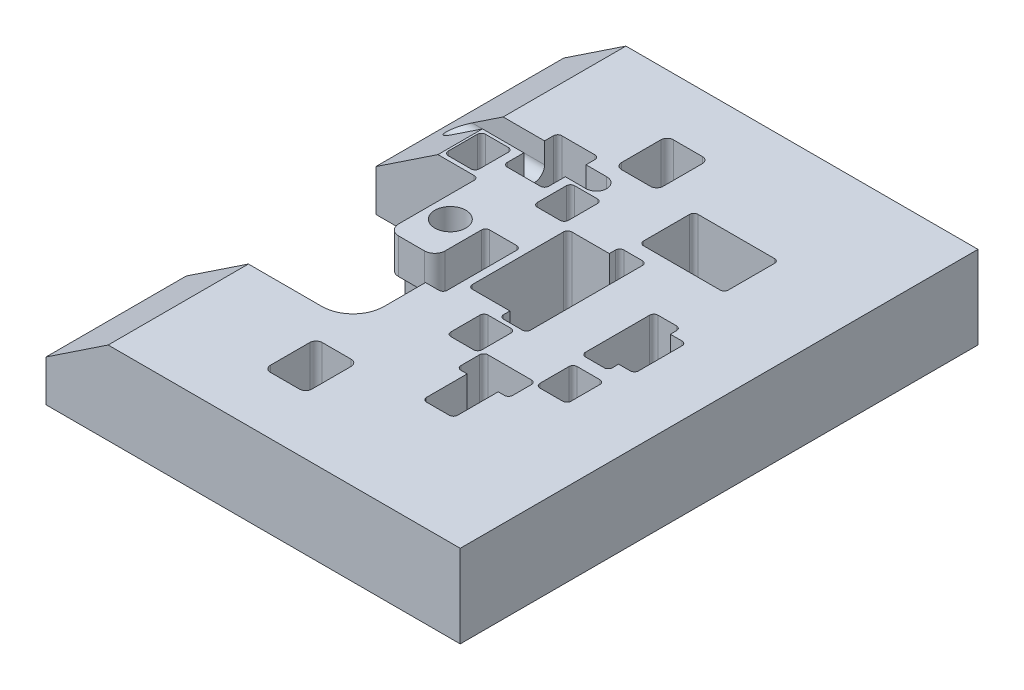
SolidWorks part; units mm, degrees
material "K110"
ref_plane "Front Plane" through (0, 0, 0) normal (0, 0, 1) x (1, 0, 0)
ref_plane "Top Plane" through (0, 0, 0) normal (0, 1, 0) x (1, 0, 0)
ref_plane "Right Plane" through (0, 0, 0) normal (1, 0, 0) x (0, 0, -1)
sketch "Sketch1" plane through (0, 0, 0) normal (0, 1, 0) x (1, 0, 0)
  line L1 (-100, -125) -> (100, -125)
  line L2 (-100, -125) -> (-100, 125)
  line L3 (-100, 125) -> (100, 125)
  line L4 (100, -125) -> (100, 125)
  line L5 (-100, -125) -> (100, 125) construction
  line L6 (-100, 125) -> (100, -125) construction
  point P0 (0, 0)
  dimension "D1" = 250
  dimension "D2" = 200
extrude "Boss-Extrude1" add sketch "Sketch1" along normal blind 40
sketch "Sketch2" plane through (0, 40, 0) normal (0, 1, 0) x (1, 0, 0)
  line L0 (17.25, 55.73) -> (55.25, 55.73) construction
  line L1 (15.75, 32.73) -> (15.75, -12.27) construction
  line L2 (58.25, 13.73) -> (58.25, -8.27) construction
  line L3 (30.25, -47.4) -> (42.25, -47.4) construction
  line L4 (17.25, 55.73) -> (55.25, 55.73)
  line L5 (15.75, 32.73) -> (15.75, -12.27)
  line L6 (58.25, 13.73) -> (58.25, -8.27)
  line L7 (30.25, -47.4) -> (42.25, -47.4)
sketch "Sketch3" plane through (0, 40, 0) normal (0, 1, 0) x (1, 0, 0)
  line L0 (30.25, -47.4) -> (42.25, -47.4) construction
  line L1 (28.75, -72.03) -> (43.75, -72.03)
  line L2 (28.75, -72.03) -> (28.75, -50.4)
  line L3 (23.75, -37.4) -> (48.75, -37.4)
  line L4 (43.75, -72.03) -> (43.75, -50.4)
  line L8 (36.25, -37.4) -> (36.25, -72.03) construction
  line L9 (36.25, 69.53) -> (36.25, -69.53) construction
  line L11 (43.75, -50.4) -> (48.75, -50.4)
  line L12 (48.75, -50.4) -> (48.75, -37.4)
  line L13 (28.75, -50.4) -> (23.75, -50.4)
  line L14 (23.75, -50.4) -> (23.75, -37.4)
  line L15 (66.38, -69.53) -> (-4.87, -69.53) construction
  dimension "D1" = 10
  dimension "D2" = 15
  dimension "D3" = 3
  dimension "D4" = 25
  dimension "D5" = 2.5
extrude "Cut-Extrude2" cut sketch "Sketch3" against normal up to next contours L3 L12 L11 L4 L1 L2 L13 L14
fillet "Fillet3" radius 2 6 edges at (43.75, 20, 72.03) (28.75, 20, 72.03) (48.75, 20, 50.4) (23.75, 20, 50.4) (48.75, 20, 37.4) (23.75, 20, 37.4)
sketch "Sketch4" plane through (0, 40, 0) normal (0, 1, 0) x (1, 0, 0)
  line L0 (48.25, -14.77) -> (61.25, -14.77)
  line L5 (61.25, -14.77) -> (61.25, -9.77)
  line L6 (64.38, 13.73) -> (58.25, 13.73) construction
  line L7 (66.38, 69.53) -> (66.38, -69.53) construction
  line L8 (66.38, 2.73) -> (51.7072, 2.73) construction
  line L9 (66.38, -6.27) -> (66.38, 11.73) construction
  line L10 (61.25, -9.77) -> (68.88, -9.77)
  line L11 (68.88, -9.77) -> (68.88, 15.23)
  line L13 (68.88, 15.23) -> (61.25, 15.23)
  line L14 (61.25, 15.23) -> (61.25, 20.23)
  line L15 (61.25, 20.23) -> (48.25, 20.23)
  line L16 (48.25, 20.23) -> (48.25, -14.77)
  line L17 (58.25, 13.73) -> (58.25, -8.27) construction
  dimension "D1" = 1.5
  dimension "D2" = 5
  dimension "D3" = 2.5
  dimension "D4" = 10
  dimension "D5" = 3
extrude "Cut-Extrude3" cut sketch "Sketch4" against normal up to next
fillet "Fillet4" radius 2 6 edges at (68.88, 20, 9.77) (68.88, 20, -15.23) (61.25, 20, -20.23) (48.25, 20, -20.23) (48.25, 20, 14.77) (61.25, 20, 14.77)
sketch "Sketch5" plane through (0, 40, 0) normal (0, 1, 0) x (1, 0, 0)
  line L0 (-7.37, -13.77) -> (12.75, -13.77)
  line L2 (12.75, -18.77) -> (25.75, -18.77)
  line L3 (25.75, -18.77) -> (25.75, 39.23)
  line L4 (25.75, 39.23) -> (12.75, 39.23)
  line L5 (12.75, 39.23) -> (12.75, 34.23)
  line L6 (12.75, 34.23) -> (-7.37, 34.23)
  line L7 (-7.37, 34.23) -> (-7.37, -13.77)
  line L8 (15.75, 32.73) -> (15.75, -12.27) construction
  line L9 (-4.87, 69.53) -> (-4.87, -69.53) construction
  line L10 (-4.87, 10.23) -> (25.75, 10.23) construction
  line L11 (-4.87, 26.73) -> (-4.87, -6.27) construction
  line L12 (12.75, -18.77) -> (12.75, -13.77)
  line L13 (1.13, -12.27) -> (15.75, -12.27) construction
  line L17 (-18, -8.27) -> (-18, 13.73) construction
  line L18 (-18, 2.73) -> (-15, 2.73) construction
  dimension "D1" = 3
  dimension "D2" = 10
  dimension "D3" = 2.5
  dimension "D4" = 1.5
  dimension "D5" = 5
extrude "Cut-Extrude4" cut sketch "Sketch5" against normal up to next
fillet "Fillet5" radius 2 6 edges at (25.75, 20, -39.23) (12.75, 20, 18.77) (25.75, 20, 18.77) (-7.37, 20, 13.77) (12.75, 20, -39.23) (-7.37, 20, -34.23)
sketch "Sketch6" plane through (0, 40, 0) normal (0, 1, 0) x (1, 0, 0)
  line L0 (15.75, 72.03) -> (15.75, 45.73)
  line L3 (15.75, 45.73) -> (56.75, 45.73)
  line L6 (56.75, 45.73) -> (56.75, 72.03)
  line L7 (56.75, 72.03) -> (15.75, 72.03)
  line L8 (36.25, 69.53) -> (36.25, 45.73) construction
  line L9 (36.25, 69.53) -> (36.25, -69.53) construction
  line L10 (66.38, 69.53) -> (-4.87, 69.53) construction
  line L12 (17.25, 55.73) -> (55.25, 55.73) construction
  dimension "D1" = 2.5
  dimension "D2" = 41
  dimension "D5" = 10
extrude "Cut-Extrude5" cut sketch "Sketch6" against normal up to next
fillet "Fillet6" radius 2 4 edges at (15.75, 20, -72.03) (56.75, 20, -72.03) (15.75, 20, -45.73) (56.75, 20, -45.73)
sketch "Sketch7" plane through (0, 40, 0) normal (0, 1, 0) x (1, 0, 0)
  line L0 (57.75, -29.77) -> (57.75, -32.27) construction
  line L3 (60.25, -29.77) -> (55.25, -29.77) construction
  line L4 (60.25, -27.27) -> (60.25, -32.27) construction
  line L5 (55.25, -11.27) -> (55.25, -38.4) construction
  line L7 (63.25, -20.77) -> (52.25, -20.77)
  line L8 (65.25, -22.77) -> (65.25, -36.77)
  line L9 (63.25, -38.77) -> (52.25, -38.77)
  line L10 (50.25, -22.77) -> (50.25, -36.77)
  arc A2 (52.25, -38.77) -> (50.25, -36.77) centre (52.25, -36.77) cw
  arc A3 (65.25, -36.77) -> (63.25, -38.77) centre (63.25, -36.77) cw
  arc A4 (63.25, -20.77) -> (65.25, -22.77) centre (63.25, -22.77) cw
  arc A5 (52.25, -20.77) -> (50.25, -22.77) centre (52.25, -22.77) ccw
  point P14 (50.25, -38.77)
  point P17 (65.25, -38.77)
  point P20 (65.25, -20.77)
  dimension "D4" = 2
  dimension "D1" = 2.5
  dimension "D2" = 18
  dimension "D3" = 15
  dimension "D5" = 9
extrude "Cut-Extrude6" cut sketch "Sketch7" against normal up to next
sketch "Sketch8" plane through (0, 40, 0) normal (0, 1, 0) x (1, 0, 0)
  line L0 (12.25, -29.77) -> (17.25, -29.77) construction
  line L3 (12.25, -32.27) -> (12.25, -27.27) construction
  line L4 (63.25, -20.77) -> (52.25, -20.77) construction
  line L7 (17.25, -38.4) -> (17.25, -13.77) construction
  line L8 (14.75, -29.77) -> (14.75, -32.27) construction
  line L9 (52.25, -38.77) -> (63.25, -38.77) construction
  line L10 (9.25, -20.77) -> (20.25, -20.77)
  line L11 (7.25, -22.77) -> (7.25, -36.77)
  line L12 (9.25, -38.77) -> (20.25, -38.77)
  line L13 (22.25, -22.77) -> (22.25, -36.77)
  arc A2 (7.25, -36.77) -> (9.25, -38.77) centre (9.25, -36.77) ccw
  arc A3 (20.25, -38.77) -> (22.25, -36.77) centre (20.25, -36.77) ccw
  arc A4 (20.25, -20.77) -> (22.25, -22.77) centre (20.25, -22.77) cw
  arc A5 (9.25, -20.77) -> (7.25, -22.77) centre (9.25, -22.77) ccw
  dimension "D1" = 2.5
  dimension "D2" = 2
extrude "Cut-Extrude7" cut sketch "Sketch8" against normal up to next
sketch "Sketch21" plane through (0, 40, 0) normal (0, 1, 0) x (1, 0, 0)
  line L0 (-21, 55.73) -> (-21, 16.73) construction
  line L3 (-24, 54.23) -> (-13, 54.23)
  line L4 (-26, 52.23) -> (-26, 38.23)
  line L5 (-24, 36.23) -> (-13, 36.23)
  line L6 (-11, 52.23) -> (-11, 38.23)
  line L7 (-21, 55.73) -> (-59, 55.73) construction
  line L9 (-16, 45.23) -> (-21, 45.23) construction
  line L10 (-18.5, 45.23) -> (-18.5, 54.23) construction
  line L11 (-40, 55.73) -> (-40, 36.23) construction
  line L12 (-16, 42.73) -> (-16, 47.73) construction
  line L16 (-69, 52.23) -> (-69, 38.23)
  line L17 (-56, 36.23) -> (-67, 36.23)
  line L18 (-54, 52.23) -> (-54, 38.23)
  line L19 (-56, 54.23) -> (-67, 54.23)
  arc A2 (-26, 38.23) -> (-24, 36.23) centre (-24, 38.23) ccw
  arc A3 (-13, 36.23) -> (-11, 38.23) centre (-13, 38.23) ccw
  arc A4 (-13, 54.23) -> (-11, 52.23) centre (-13, 52.23) cw
  arc A5 (-24, 54.23) -> (-26, 52.23) centre (-24, 52.23) ccw
  arc A6 (-56, 54.23) -> (-54, 52.23) centre (-56, 52.23) cw
  arc A7 (-67, 54.23) -> (-69, 52.23) centre (-67, 52.23) ccw
  arc A8 (-67, 36.23) -> (-69, 38.23) centre (-67, 38.23) cw
  arc A9 (-54, 38.23) -> (-56, 36.23) centre (-56, 38.23) cw
  dimension "D4" = 15
  dimension "D2" = 2
  dimension "D1" = 2.5
  dimension "D3" = 18
extrude "Cut-Extrude12" cut sketch "Sketch21" against normal up to next
sketch "Sketch22" plane through (0, 40, 0) normal (0, 1, 0) x (1, 0, 0)
  line L0 (-100, 125) -> (-100, -125) construction
  line L1 (-100, 55.73) -> (-15, 55.73)
  line L2 (-100, 55.73) -> (-100, 65.726)
  line L3 (-100, 65.726) -> (-15, 65.726)
  line L4 (-15, 55.73) -> (-15, 65.726)
  line L5 (-21, 55.73) -> (-59, 55.73) construction
  line L6 (-59, 63.776) -> (-21, 63.776) construction
  line L7 (-21, 55.73) -> (-21, 61.5256) construction
  line L8 (-15, 60.728) -> (-100, 60.728) construction
  dimension "D1" = 1.95
  dimension "D2" = 6
ref_plane "Plane1" through (0, 0, -60.728) normal (0, 0, -1) x (-1, 0, 0)
sketch "Sketch24" plane through (0, 0, -60.728) normal (0, 0, -1) x (-1, 0, 0)
  line L0 (15, 40) -> (15, 35)
  line L1 (15, 40) -> (100, 40) construction
  line L2 (25, 25) -> (100, 25)
  line L3 (100, 40) -> (100, 0) construction
  line L4 (15, 40) -> (100, 40)
  line L5 (100, 40) -> (100, 25)
  arc A0 (15, 35) -> (25, 25) centre (25, 35) ccw
  dimension "D2" = 10
  dimension "D1" = 15
extrude "Cut-Extrude15" cut sketch "Sketch24" against normal mid plane 10
fillet "Fillet9" 2 edges at (-62.5, 25, -55.728) (-62.5, 25, -65.728) type full round first side face at (-50.5858, 32.5858, -55.728) second side face at (-50.5858, 32.5858, -65.728) middle face at (-62.5, 25, -60.728)
sketch "Sketch23" plane through (0, 40, 0) normal (0, 1, 0) x (1, 0, 0)
  line L0 (-40, 55.73) -> (-40, 45.73) construction
  line L1 (-48, 72.03) -> (-32, 72.03)
  line L2 (-50, 70.03) -> (-50, 47.73)
  line L3 (-48, 45.73) -> (-32, 45.73)
  line L4 (-30, 70.03) -> (-30, 47.73)
  line L5 (-21, 55.73) -> (-59, 55.73) construction
  line L6 (17.75, 45.73) -> (54.75, 45.73) construction
  line L7 (54.75, 72.03) -> (17.75, 72.03) construction
  arc A0 (-50, 47.73) -> (-48, 45.73) centre (-48, 47.73) ccw
  arc A1 (-48, 72.03) -> (-50, 70.03) centre (-48, 70.03) ccw
  arc A2 (-32, 72.03) -> (-30, 70.03) centre (-32, 70.03) cw
  arc A3 (-32, 45.73) -> (-30, 47.73) centre (-32, 47.73) ccw
  point P14 (-50, 45.73)
  point P21 (-30, 45.73)
  dimension "D2" = 2
  dimension "D1" = 20
extrude "Cut-Extrude14" cut sketch "Sketch23" against normal up to next
sketch "Sketch26" plane through (0, 40, 0) normal (0, 1, 0) x (1, 0, 0)
  line L0 (-100, 55.728) -> (-100, -125) construction
  line L1 (-100, 34.23) -> (-50.5, 34.23)
  line L2 (-100, 34.23) -> (-100, -57.27)
  line L3 (-100, -57.27) -> (-19.5, -57.27)
  line L4 (-19.5, -22.27) -> (-19.5, -57.27)
  line L5 (-60.5, 32.73) -> (-66.5, 32.73) construction
  line L6 (-50.5, 34.23) -> (-50.5, -9.27)
  line L7 (-50.5, -9.27) -> (-28, -9.27)
  line L8 (-59, -19.27) -> (-21, -19.27) construction
  line L9 (-21, -11.27) -> (-21, -19.27) construction
  line L10 (-28, -9.27) -> (-28, 15.23)
  line L11 (-60.5, -12.27) -> (-60.5, 32.73) construction
  line L12 (-19.5, -22.27) -> (-11, -22.27)
  line L13 (-11, -22.27) -> (-11, 15.23)
  line L14 (-28, 15.23) -> (-11, 15.23)
  line L15 (-18, -8.27) -> (-18, 13.73) construction
  line L16 (-12, 13.73) -> (-18, 13.73) construction
  dimension "D1" = 1.5
  dimension "D2" = 10
  dimension "D3" = 1.5
  dimension "D4" = 35
  dimension "D5" = 10
  dimension "D6" = 1.5
  dimension "D7" = 3
  dimension "D8" = 10
  dimension "D9" = 7
extrude "Cut-Extrude16" cut sketch "Sketch26" against normal up to next contours L1 L6 L7 L10 L14 L13 L12 L4 L3 L2
fillet "Fillet10" radius 2 4 edges at (-11, 20, 22.27) (-50.5, 20, -34.23) (-11, 20, -15.23) (-28, 20, -15.23)
sketch "Sketch27" plane through (-50.5, 0, 0) normal (-1, 0, 0) x (0, 0, 1)
  line L0 (-32.23, 0) -> (9.27, 0) construction
  line L1 (1.27, 0) -> (9.27, 0)
  line L2 (1.27, 0) -> (1.27, 23)
  line L3 (1.27, 23) -> (9.27, 23)
  line L4 (9.27, 0) -> (9.27, 23)
  line L5 (9.27, 23) -> (9.27, 0) construction
  dimension "D1" = 23
  dimension "D2" = 8
extrude "Cut-Extrude17" cut sketch "Sketch27" against normal blind 18.5 contours L4 L3 L2 L1
fillet "Fillet11" radius 3 3 edges at (-32, 23, 5.27) (-41.25, 23, 1.27) (-32, 11.5, 1.27)
fillet "Fillet12" radius 15 1 edges at (-19.5, 20, 57.27)
fillet "Fillet13" radius 5 2 edges at (-50.5, 31.5, 9.27) (-28, 20, 9.27)
chamfer "Chamfer1" distance 20 distance2 30 2 edges at (-100, 40, -44.979) (-100, 40, 91.135) first distance on face at (-100, 26.875, -70.1715) first distance on face at (-100, 20, 91.135)
sketch "Sketch28" plane through (0, 40, 0) normal (0, 1, 0) x (1, 0, 0)
  line L0 (-14.87, 84.765) -> (-9.87, 84.765) construction
  line L1 (-19.37, 97.265) -> (-5.37, 97.265)
  line L2 (-22.37, 94.265) -> (-22.37, 75.265)
  line L3 (-19.37, 72.265) -> (-5.37, 72.265)
  line L4 (-2.37, 94.265) -> (-2.37, 75.265)
  line L5 (-14.87, 95) -> (-14.87, 74.53) construction
  line L6 (-9.87, 50.73) -> (-9.87, 95) construction
  line L7 (-12.37, 84.765) -> (-12.37, 92.265) construction
  line L8 (-12.37, 92.265) -> (-12.37, 77.265) construction
  line L9 (-9.64, 92.265) -> (-9.64, 77.265) construction
  line L10 (-15.1, 92.265) -> (-15.1, 77.265) construction
  arc A0 (-9.64, 92.265) -> (-15.1, 92.265) centre (-12.37, 92.265) ccw construction
  arc A1 (-15.1, 77.265) -> (-9.64, 77.265) centre (-12.37, 77.265) ccw construction
  arc A2 (-22.37, 75.265) -> (-19.37, 72.265) centre (-19.37, 75.265) ccw
  arc A3 (-5.37, 72.265) -> (-2.37, 75.265) centre (-5.37, 75.265) ccw
  arc A4 (-5.37, 97.265) -> (-2.37, 94.265) centre (-5.37, 94.265) cw
  arc A5 (-19.37, 97.265) -> (-22.37, 94.265) centre (-19.37, 94.265) ccw
  point P12 (-12.37, 84.765)
  point P18 (0, 0)
  point P19 (0, 0)
  point P20 (0, 0)
  point P21 (0, 0)
  point P26 (-2.37, 72.265)
  point P29 (-2.37, 97.265)
  point P32 (-22.37, 97.265)
  dimension "D4" = 2.73
  dimension "D5" = 3
  dimension "D1" = 25
  dimension "D2" = 20
  dimension "D3" = 15
extrude "Cut-Extrude18" cut sketch "Sketch28" against normal up to next
mirror "Mirror1" about plane through (0, 0, 0) normal (0, 0, 1) of "Cut-Extrude18"
extrude "Cut-Extrude21" cut sketch "Sketch31" against normal through all
sketch "Sketch31" plane through (452.63, 40, 0) normal (0, 1, 0) x (1, 0, 0)
  circle A0 centre (-492.63, 10.23) radius 7.5
